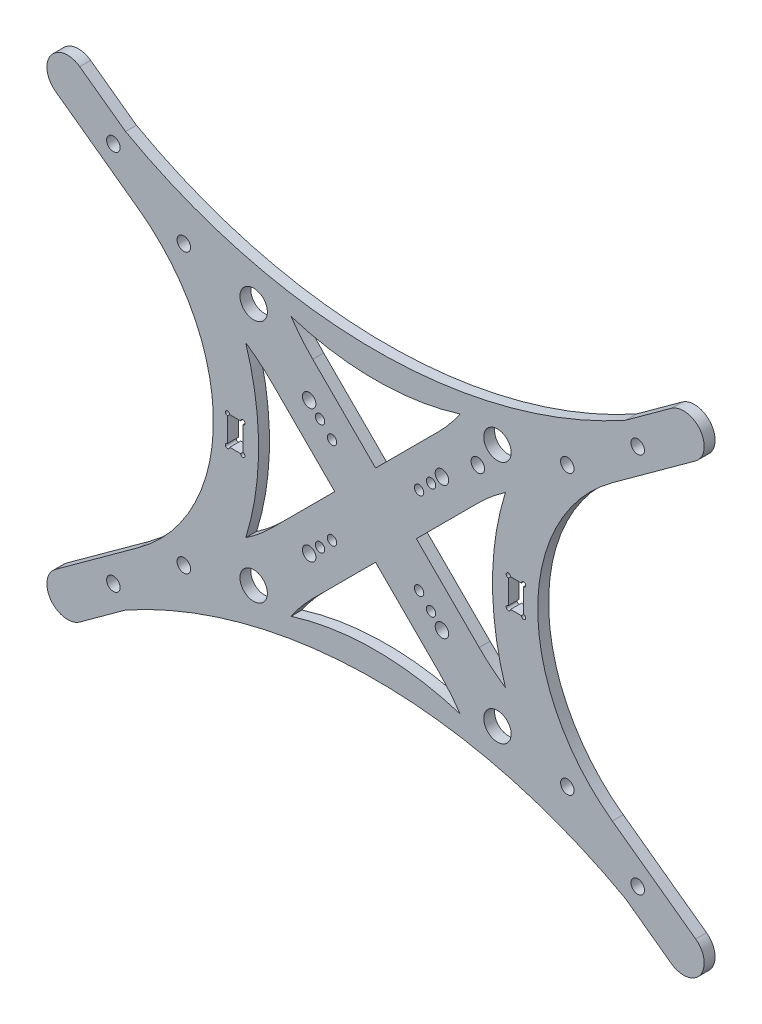
SolidWorks part; units mm, degrees
material "PPS"
ref_plane "前视基准面" through (0, 0, 0) normal (0, 0, 1) x (1, 0, 0)
ref_plane "上视基准面" through (0, 0, 0) normal (0, 1, 0) x (1, 0, 0)
ref_plane "右视基准面" through (0, 0, 0) normal (1, 0, 0) x (0, 0, -1)
sketch "草图7" plane through (0, 0, 0) normal (0, 0, 1) x (1, 0, 0)
  line L0 (-137.4469, 0) -> (193.7386, 0) construction
  line L1 (0, 90.5001) -> (0, -188.7446) construction
  line L2 (0, 0) -> (86.3378, -62.728) construction
  line L61 (-67.9485, -55.2388) -> (-57.4206, -47.5898)
  line L62 (-73.5325, -47.5531) -> (-54.395, -33.649)
  line L66 (-67.9485, 55.2388) -> (-57.4206, 47.5898)
  line L82 (-73.5325, 47.5531) -> (-54.395, 33.649)
  line L93 (73.5325, 47.5531) -> (54.395, 33.649)
  line L94 (-34, -3.25) -> (-34, 3.25) construction
  line L95 (67.9485, 55.2388) -> (57.4206, 47.5898)
  line L104 (15.25, 15.25) -> (0, 0) construction
  line L105 (67.9485, -55.2388) -> (57.4206, -47.5898)
  line L106 (73.5325, -47.5531) -> (54.395, -33.649)
  line L107 (0, 0) -> (86.3378, 62.728) construction
  circle A40 centre (10, 10) radius 1.075
  circle A65 centre (12.75, 12.75) radius 1.075
  circle A66 centre (15.25, 15.25) radius 1.55
  circle A73 centre (15.25, -15.25) radius 1.55
  circle A74 centre (12.75, -12.75) radius 1.075
  circle A75 centre (10, -10) radius 1.075
  circle A76 centre (28, -28) radius 3.15
  circle A89 centre (28, 28) radius 3.15
  arc A132 (67.9485, 55.2388) -> (73.5325, 47.5531) centre (70.7405, 51.396) cw
  arc A133 (54.395, 33.649) -> (54.395, -33.649) centre (78.8424, 0) ccw
  circle A134 centre (60.2246, 43.7557) radius 1.55
  arc A135 (-57.4206, -47.5898) -> (57.4206, -47.5898) centre (0, -151.3241) cw
  circle A136 centre (-60.2246, 43.7557) radius 1.55
  arc A138 (-54.395, 33.649) -> (-54.395, -33.649) centre (-78.8424, 0) cw
  arc A139 (-67.9485, 55.2388) -> (-73.5325, 47.5531) centre (-70.7405, 51.396) ccw
  circle A152 centre (-28, 28) radius 3.15
  circle A153 centre (-28, -28) radius 3.15
  circle A154 centre (-10, -10) radius 1.075
  circle A155 centre (-12.75, -12.75) radius 1.075
  circle A156 centre (-15.25, -15.25) radius 1.55
  circle A157 centre (-15.25, 15.25) radius 1.55
  circle A158 centre (-12.75, 12.75) radius 1.075
  circle A159 centre (-10, 10) radius 1.075
  arc A166 (-57.4206, 47.5898) -> (57.4206, 47.5898) centre (0, 151.3241) ccw
  arc A167 (67.9485, -55.2388) -> (73.5325, -47.5531) centre (70.7405, -51.396) ccw
  arc A172 (-67.9485, -55.2388) -> (-73.5325, -47.5531) centre (-70.7405, -51.396) cw
  circle A176 centre (60.2246, -43.7557) radius 1.55
  circle A177 centre (44.0442, -32) radius 1.55
  circle A178 centre (44.0442, 32) radius 1.55
  circle A179 centre (-44.0442, 32) radius 1.55
  circle A180 centre (-60.2246, -43.7557) radius 1.55
  circle A181 centre (-44.0442, -32) radius 1.55
  point P49 (-37.25, 0)
  dimension "D2" = 2.75
  dimension "D4" = 2.5
  dimension "D1" = 2.15
  dimension "D3" = 3.1
  dimension "D6" = 3.1
  dimension "D10" = 10
  dimension "D5" = 45
  dimension "D7" = 4.75
  dimension "D8" = 3.25
  dimension "D9" = 10
  dimension "D11" = 12.75
  dimension "D16" = 36
sketch "草图8" plane through (0, 0, 0) normal (0, 0, 1) x (1, 0, 0)
  line L0 (-96.7808, 0) -> (86.8563, 0) construction
  line L1 (0, 52.226) -> (0, -62.4511) construction
  line L2 (34, -3.25) -> (30.5, -3.25)
  line L3 (-34, 3.25) -> (-30.5, 3.25)
  line L4 (-34, 3.25) -> (-34, -3.25)
  line L5 (-34, -3.25) -> (-30.5, -3.25)
  line L6 (-30.5, 3.25) -> (-30.5, -3.25)
  line L7 (30.5, 3.25) -> (30.5, -3.25)
  line L8 (34, 3.25) -> (30.5, 3.25)
  line L9 (34, 3.25) -> (34, -3.25)
  dimension "D1" = 30.5
  dimension "D2" = 6.5
  dimension "D3" = 3.5
sketch "草图6" plane through (0, 0, 0) normal (0, 0, 1) x (1, 0, 0)
  line L3 (-23.8014, 14.4296) -> (-9.3719, 0)
  line L9 (-58.8867, 0) -> (57.6096, 0) construction
  line L14 (-23.8014, -14.4296) -> (-9.3719, 0)
  line L15 (0, 29.8455) -> (0, -115.5328) construction
  line L29 (14.4296, 23.8014) -> (0, 9.3719)
  line L30 (-14.4296, 23.8014) -> (0, 9.3719)
  line L31 (23.8014, -14.4296) -> (9.3719, 0)
  line L32 (23.8014, 14.4296) -> (9.3719, 0)
  line L33 (-14.4296, -23.8014) -> (0, -9.3719)
  line L34 (14.4296, -23.8014) -> (0, -9.3719)
  arc A18 (-23.8014, 14.4296) -> (-29.8202, 19.4008) centre (-52.8883, -14.6573) ccw
  arc A19 (-23.8014, -14.4296) -> (-29.8202, -19.4008) centre (-52.8883, 14.6573) cw
  arc A20 (-29.8202, -19.4008) -> (-29.8202, 19.4008) centre (-91.9966, 0) ccw
  arc A33 (-14.4296, 23.8014) -> (-19.4008, 29.8202) centre (14.6573, 52.8883) cw
  arc A34 (-19.4008, 29.8202) -> (19.4008, 29.8202) centre (0, 91.9966) ccw
  arc A35 (14.4296, 23.8014) -> (19.4008, 29.8202) centre (-14.6573, 52.8883) ccw
  arc A36 (23.8014, 14.4296) -> (29.8202, 19.4008) centre (52.8883, -14.6573) cw
  arc A37 (29.8202, 19.4008) -> (29.8202, -19.4008) centre (91.9966, 0) ccw
  arc A38 (23.8014, -14.4296) -> (29.8202, -19.4008) centre (52.8883, 14.6573) ccw
  arc A39 (14.4296, -23.8014) -> (19.4008, -29.8202) centre (-14.6573, -52.8883) cw
  arc A40 (19.4008, -29.8202) -> (-19.4008, -29.8202) centre (0, -91.9966) ccw
  arc A41 (-14.4296, -23.8014) -> (-19.4008, -29.8202) centre (14.6573, -52.8883) ccw
  point P49 (0, 0)
  dimension "D1" = 4
extrude "主结构-厚度还是得2.5, 不然铝柱不好选" add sketch "草图7" along normal blind 2.5
extrude "切除-拉伸2" cut sketch "草图6" along normal through all
extrude "切除-拉伸3" cut sketch "草图8" along normal through all
sketch "计算机板和PCB结构" plane through (0, 0, 0) normal (0, 0, 1) x (1, 0, 0)
  line L5 (0, 0) -> (0, 133.3353) construction
  line L6 (0, 0) -> (133.1914, 0) construction
  circle A1 centre (23.5, 21.7128) radius 1.55
  circle A9 centre (23.5, 21.7128) radius 1.55 construction
  circle A10 centre (-32, 42) radius 1.55
  circle A11 centre (32, 42) radius 1.55
  circle A12 centre (32, 42) radius 1.55 construction
  circle A13 centre (-32, 42) radius 1.55 construction
  circle A14 centre (-36, -43) radius 1.55
  circle A15 centre (36, -43) radius 1.55
  circle A16 centre (-29.25, -40.5) radius 1.55
  circle A17 centre (29.25, -40.5) radius 1.55
  circle A18 centre (-17.5, 47.5) radius 1.55
  circle A19 centre (17.5, 47.5) radius 1.55
extrude "计算机板孔位和PCB孔位" cut sketch "计算机板和PCB结构" along normal through all contours A10 | A18 | A19 | A11 | A1 | A14 | A16 | A17 | A15 region at (23.5, 21.7128, 0) region at (-32, 42, 0) region at (32, 42, 0) region at (-36, -43, 0) region at (36, -43, 0) region at (-29.25, -40.5, 0) region at (29.25, -40.5, 0) region at (-17.5, 47.5, 0) region at (17.5, 47.5, 0)
sketch "草图9" plane through (0, 0, 2.5) normal (0, 0, 1) x (1, 0, 0)
  line L0 (0, 0) -> (0, 67.9961) construction
  circle A0 centre (-34, 3.25) radius 0.5
  circle A1 centre (-30.5, 3.25) radius 0.5
  circle A2 centre (-30.5, -3.25) radius 0.5
  circle A3 centre (-34, -3.25) radius 0.5
  circle A4 centre (34, -3.25) radius 0.5
  circle A5 centre (30.5, -3.25) radius 0.5
  circle A6 centre (30.5, 3.25) radius 0.5
  circle A7 centre (34, 3.25) radius 0.5
  dimension "D1" = 1
extrude "直角约束" cut sketch "草图9" against normal through all
